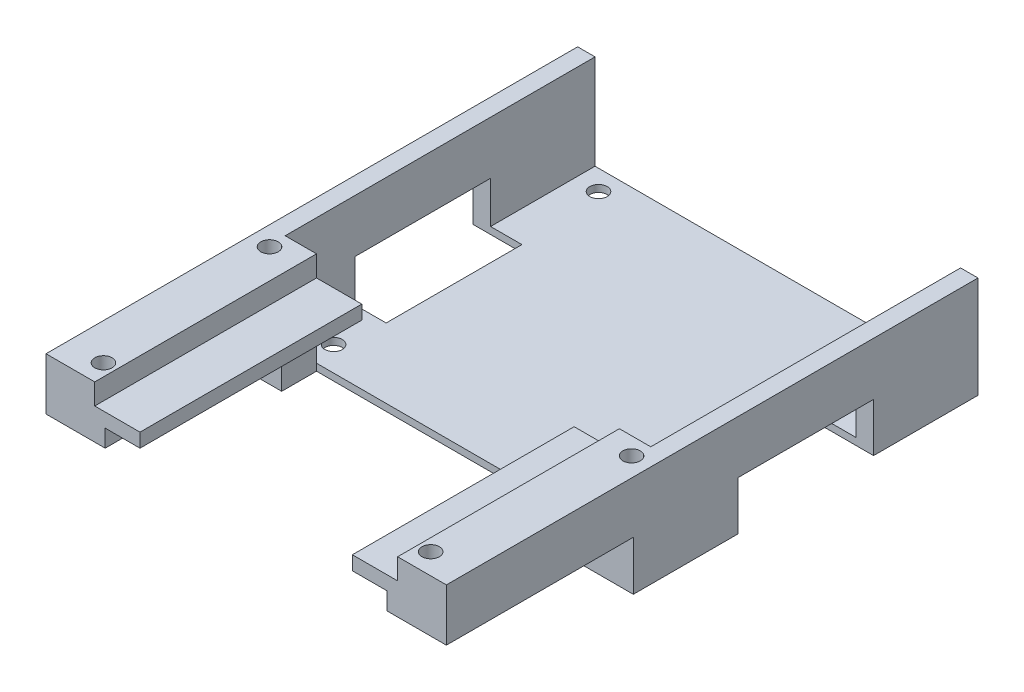
SolidWorks part; units mm, degrees
ref_plane "Front Plane" through (0, 0, 0) normal (0, 0, 1) x (1, 0, 0)
ref_plane "Top Plane" through (0, 0, 0) normal (0, 1, 0) x (1, 0, 0)
ref_plane "Right Plane" through (0, 0, 0) normal (1, 0, 0) x (0, 0, -1)
sketch "Sketch1" plane through (0, 0, 0) normal (0, 1, 0) x (1, 0, 0)
  line L0 (0, 0) -> (0, 76.35) construction
  line L1 (-28.75, 76.35) -> (28.75, 76.35)
  line L2 (28.75, 76.35) -> (28.75, 0)
  line L3 (28.75, 0) -> (21.75, 0)
  line L4 (21.75, 0) -> (21.75, 31.85)
  line L5 (21.75, 31.85) -> (-21.75, 31.85)
  line L6 (-21.75, 31.85) -> (-21.75, 0)
  line L7 (-21.75, 0) -> (-28.75, 0)
  line L8 (-28.75, 0) -> (-28.75, 76.35)
  line L9 (-26.25, 76.35) -> (-26.25, 31.85)
  line L14 (-26.25, 31.85) -> (-21.75, 31.85)
  line L15 (26.25, 76.35) -> (26.25, 31.85)
  line L16 (26.25, 31.85) -> (21.75, 31.85)
  line L17 (28.75, 74.35) -> (30.25, 74.35)
  line L18 (-28.75, 41.35) -> (-26.25, 41.35)
  line L19 (-28.75, 41.35) -> (-28.75, 53.35)
  line L20 (-28.75, 53.35) -> (-26.25, 53.35)
  line L21 (-26.25, 41.35) -> (-26.25, 53.35)
  line L22 (30.25, 68.35) -> (28.75, 68.35)
  line L23 (-30.25, 68.35) -> (-28.75, 68.35)
  line L24 (-28.75, 74.35) -> (-30.25, 74.35)
  arc A0 (30.25, 68.35) -> (30.25, 74.35) centre (30.25, 71.35) ccw
  arc A1 (-30.25, 68.35) -> (-30.25, 74.35) centre (-30.25, 71.35) cw
  point P10 (0, 76.35)
  point P16 (-27.5, 41.35)
  point P17 (-22.85, 73.45)
  point P18 (22.85, 73.45)
  point P23 (22.85, 35.4)
  point P24 (-22.85, 35.4)
  point P25 (23.5, 3)
  point P26 (26, 29.35)
  point P27 (-26, 29.35)
  point P28 (-23.5, 3)
  point P40 (30.25, 71.35)
  point P41 (-30.25, 71.35)
  dimension "D16" = 3
  dimension "D1" = 2.5
  dimension "D2" = 7
  dimension "D3" = 43.5
  dimension "D4" = 31.85
  dimension "D5" = 44.5
  dimension "D6" = 23
  dimension "D7" = 12
  dimension "D8" = 22.85
  dimension "D9" = 38.05
  dimension "D10" = 2.9
  dimension "D11" = 47
  dimension "D12" = 52
  dimension "D13" = 47
  dimension "D14" = 3
  dimension "D15" = 1.5
  dimension "D17" = 2
extrude "Boss-Extrude1" add sketch "Sketch1" along normal blind 1 contours L5 L0 L1 L9 L14 | L0 L5 L16 L15 L1 region at (-13.125, 0, -54.1) region at (13.125, 0, -54.1)
extrude "Boss-Extrude2" add sketch "Sketch1<3>" along normal blind 14.6 contours L18 L8 L7 L6 L14 L9 | L8 L20 L9 L1 | L15 L16 L4 L3 L2 L1 | L20 L8 L18 L9 region at (-27.5, 0, -64.85) region at (25.999, 0, -28.6329) region at (-27.5, 0, -47.35) region at (-25.4666, 0, -17.9154)
sketch "Sketch1<3>" plane through (0, 0, 0) normal (0, 1, 0) x (1, 0, 0) same geometry as "Sketch1"
hole_wizard "Ø2.5 (2.5) Diameter Hole1" positions "Sketch4" profile "Sketch5" hole size "Ø2.5" standard "ANSI Metric" end condition through all
sketch "Sketch4" plane through (0, 0, 0) normal (0, -1, 0) x (-1, 0, 0)
  point P0 (-22.85, 73.45)
  point P3 (22.85, 73.45)
  point P6 (26, 29.35)
  point P9 (22.85, 35.4)
  point P12 (-22.85, 35.4)
  point P15 (-26, 29.35)
  point P18 (-23.5, 3)
  point P21 (23.5, 3)
  point P24 (-30.25, 71.35)
  point P27 (30.25, 71.35)
sketch "Sketch5" plane through (22.85, 0, -73.45) normal (1, 0, 0) x (0, 0, -1)
  line L0 (0, 0) -> (0, 14.6)
  line L1 (0, 14.6) -> (1.25, 14.6)
  line L2 (1.25, 14.6) -> (1.25, 0)
  line L5 (1.25, 0) -> (0, 0)
  line L11 (0, -6.35) -> (0, 107.95) construction
  dimension "Thru Hole Dia." = 2.5
  dimension "Thru Hole Depth" = 14.6
sketch "Sketch6" plane through (0, 0, 0) normal (0, 0, 1) x (1, 0, 0)
  line L0 (-21.75, 14.6) -> (-21.75, 0) construction
  line L5 (0, -1.6497) -> (0, 21.9352) construction
  line L6 (-21.75, 9.6) -> (-15.25, 9.6)
  line L7 (-21.75, 9.6) -> (-21.75, 11.6)
  line L8 (-21.75, 11.6) -> (-15.25, 11.6)
  line L9 (-15.25, 9.6) -> (-15.25, 11.6)
  line L10 (-28.75, 14.6) -> (-28.75, 0) construction
  line L11 (-20.25, 9.6) -> (-21.75, 9.6)
  line L12 (-20.25, 9.6) -> (-20.25, 7.1)
  line L13 (-20.25, 7.1) -> (-21.75, 7.1)
  line L14 (-21.75, 9.6) -> (-21.75, 7.1)
  line L15 (-21.75, 0) -> (-28.75, 0)
  line L16 (-21.75, 0) -> (-21.75, 7.1)
  line L17 (-21.75, 7.1) -> (-28.75, 7.1)
  line L18 (-28.75, 0) -> (-28.75, 7.1)
  line L19 (28.75, 0) -> (28.75, 7.1)
  line L20 (21.75, 7.1) -> (28.75, 7.1)
  line L21 (21.75, 0) -> (21.75, 7.1)
  line L22 (21.75, 0) -> (28.75, 0)
  line L23 (21.75, 9.6) -> (21.75, 7.1)
  line L24 (20.25, 7.1) -> (21.75, 7.1)
  line L25 (20.25, 9.6) -> (20.25, 7.1)
  line L26 (20.25, 9.6) -> (21.75, 9.6)
  line L27 (15.25, 9.6) -> (15.25, 11.6)
  line L28 (21.75, 11.6) -> (15.25, 11.6)
  line L29 (21.75, 9.6) -> (21.75, 11.6)
  line L30 (21.75, 9.6) -> (15.25, 9.6)
  line L31 (-21.75, 14.6) -> (-28.75, 14.6) construction
  line M21 (21.75, 0) -> (28.75, 0)
  line M22 (28.75, 0) -> (28.75, 14.6)
  line M24 (21.75, 14.6) -> (21.75, 0)
  dimension "D1" = 6.5
  dimension "D2" = 3
  dimension "D3" = 2
  dimension "D4" = 2.5
  dimension "D5" = 1.5
extrude "Boss-Extrude3" add sketch "Sketch6" against normal up to surface (31.85 mm away) contours L30 L26 L28 L27 M24 | L26 L25 L24 M24 | L6 L9 L8 L7 | L6 L14 L13 L12 region at (-18.5, 10.6, 0) region at (-21, 8.35, 0) region at (21, 8.35, 0) region at (18.5, 10.6, 0) up to face at (0, 0.5, -31.85)
extrude "Cut-Extrude1" cut sketch "Sketch6<4>" against normal blind 26.85 contours L18 L15 L16 L17 | L20 M24 M21 M22 region at (-25.25, 3.55, 0) region at (25.25, 3.55, 0)
sketch "Sketch6<4>" plane through (0, 0, 0) normal (0, 0, 1) x (1, 0, 0) same geometry as "Sketch6"
sketch "Sketch8" plane through (0, 0, 0) normal (0, -1, 0) x (1, 0, 0)
  line L0 (0, 17.5937) -> (0, -89.2896) construction
  line L1 (-28.75, -61.35) -> (-21.75, -61.35)
  line L2 (-28.75, -61.35) -> (-28.75, -41.85)
  line L3 (-28.75, -41.85) -> (-21.75, -41.85)
  line L4 (-21.75, -61.35) -> (-21.75, -41.85)
  line L6 (-28.75, -76.35) -> (28.75, -76.35) construction
  line L8 (21.75, -61.35) -> (21.75, -41.85)
  line L9 (28.75, -41.85) -> (21.75, -41.85)
  line L10 (28.75, -61.35) -> (28.75, -41.85)
  line L11 (28.75, -61.35) -> (21.75, -61.35)
  line L12 (-28.75, -26.85) -> (-28.75, -76.35) construction
  dimension "D1" = 15
  dimension "D2" = 7
  dimension "D3" = 19.5
extrude "Cut-Extrude2" cut sketch "Sketch8" against normal blind 7
sketch "Sketch9" plane through (0, 0, 0) normal (0, -1, 0) x (1, 0, 0)
  line L0 (-3.6898, -66.9636) -> (-0.7669, -56.1918)
  line L1 (-0.7669, -56.1918) -> (-9.5993, -56.1918)
  line L2 (-9.5993, -56.1918) -> (4.2079, -40.0618)
  line L3 (4.2079, -40.0618) -> (3.001, -51.0446)
  line L4 (3.001, -51.0446) -> (10.9951, -51.0446)
  line L5 (10.9951, -51.0446) -> (-3.6898, -66.9636)
  point P2 (13.301, -51.2557)
  point P7 (-0.7669, -56.1918)
extrude "Cut-Extrude3" cut sketch "Sketch9" against normal blind 0.5
equation "\"D1@Boss-Extrude2\"=16.000000mm-1.4"
